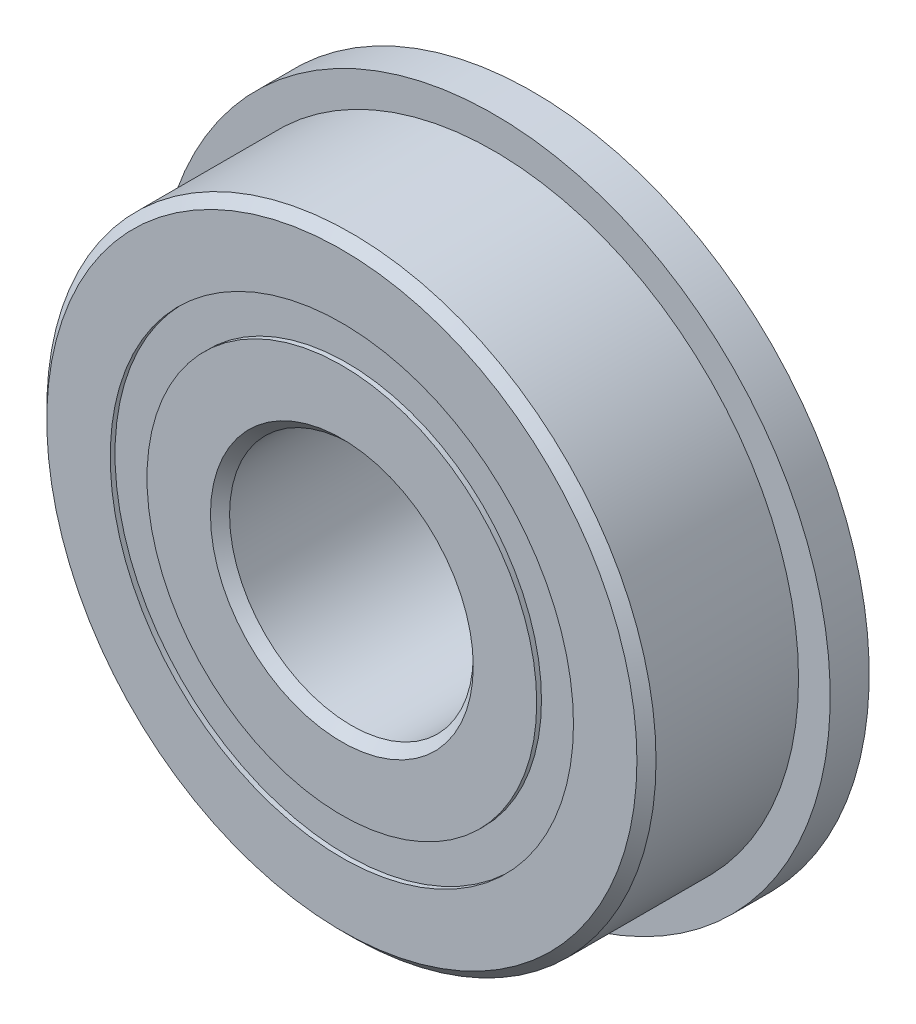
SolidWorks part; units mm, degrees
ref_plane "Front Plane" through (0, 0, 0) normal (0, 0, 1) x (1, 0, 0)
ref_plane "Top Plane" through (0, 0, 0) normal (0, 1, 0) x (1, 0, 0)
ref_plane "Right Plane" through (0, 0, 0) normal (1, 0, 0) x (0, 0, -1)
sketch "Sketch1" plane through (0, 0, 0) normal (1, 0, 0) x (0, 0, -1)
  line L0 (-2.4892, 0) -> (2.4892, 0) construction
  line L1 (0, 7.9375) -> (0, -7.9375) construction
  line L2 (2.2403, 7.9375) -> (-2.2403, 7.9375)
  line L3 (-2.2403, 7.9375) -> (-2.4892, 7.6886)
  line L4 (-2.4892, 7.6886) -> (-2.4892, 6.0352)
  line L5 (-2.4892, 6.0352) -> (-1.1063, 6.0352)
  line L6 (2.4892, 6.0352) -> (1.1063, 6.0352)
  line L7 (2.4892, 7.6886) -> (2.4892, 6.0352)
  line L8 (2.2403, 7.9375) -> (2.4892, 7.6886)
  line L9 (0, 7.9375) -> (0, 5.5563) construction
  line L10 (0, 5.5563) -> (0, 3.175) construction
  arc A0 (-1.1063, 6.0352) -> (1.1063, 6.0352) centre (0, 5.5563) cw
  point P14 (0, 3.175)
  dimension "D3" = 2.2126
  dimension "D1" = 45
  dimension "Width" = 4.9784
  dimension "OD" = 15.875
  dimension "D2" = 0.2489
  dimension "Shaft Dia" = 6.35
  dimension "D4" = 0.479
revolve "Revolve1" add sketch "Sketch1" angle 360 about L0
sketch "Sketch3" plane through (0, 0, 0) normal (1, 0, 0) x (0, 0, -1)
  line L0 (-2.4892, 5.0773) -> (-1.1063, 5.0773)
  line L1 (0, 7.9375) -> (0, -7.9375) construction
  line L2 (-2.4892, 7.6886) -> (-2.4892, 6.0352) construction
  line L3 (-2.4892, 5.0773) -> (-2.4892, 3.4239)
  line L4 (-2.2403, 7.9375) -> (-2.4892, 7.6886) construction
  line L5 (-2.4892, 3.4239) -> (-2.2403, 3.175)
  line L6 (-2.2403, 3.175) -> (2.2403, 3.175)
  line L7 (2.2403, 7.9375) -> (2.2403, -7.9375) construction
  line L8 (2.2403, 3.175) -> (2.4892, 3.4239)
  line L9 (2.4892, -7.6886) -> (2.4892, 7.6886) construction
  line L10 (2.4892, 3.4239) -> (2.4892, 5.0773)
  line L11 (2.4892, 5.0773) -> (1.1063, 5.0773)
  line L13 (2.2403, 7.9375) -> (2.4892, 7.6886) construction
  arc A0 (1.1063, 6.0352) -> (-1.1063, 6.0352) centre (0, 5.5563) ccw construction
  arc A1 (1.1063, 5.0773) -> (-1.1063, 5.0773) centre (0, 5.5562) cw
revolve "Revolve3" add sketch "Sketch3" angle 360 about L0
sketch "Sketch4" plane through (0, 0, 0) normal (1, 0, 0) x (0, 0, -1)
  line L0 (-1.2055, 5.5563) -> (1.2055, 5.5563)
  arc A2 (-1.2055, 5.5563) -> (1.2055, 5.5563) centre (0, 5.5563) cw
  arc A3 (1.1063, 6.0352) -> (-1.1063, 6.0352) centre (0, 5.5563) ccw construction
revolve "Revolve4" add sketch "Sketch4" angle 360 about L0
ref_axis "Axis1" through (0, 0, -2.4892) along (0, 0, 1)
pattern_circular "CirPattern1" count 14 every 25.714 about axis through (0, 0, -2.4892) along (0, 0, 1) of bodies 104
sketch "Sketch5" plane through (0, 0, 0) normal (1, 0, 0) x (0, 0, -1)
  line L0 (-2.4892, 6.0352) -> (-1.1063, 6.0352) construction
  line L1 (-2.3647, 6.0352) -> (-1.2055, 6.0352)
  line L2 (-2.3647, 6.0352) -> (-2.3647, 5.0773)
  line L3 (-2.3647, 5.0773) -> (-1.2055, 5.0773)
  line L4 (-1.2055, 6.0352) -> (-1.2055, 5.0773)
  line L5 (-2.4892, 5.0773) -> (-1.1063, 5.0773) construction
  line L6 (2.4892, 6.0352) -> (1.1063, 6.0352) construction
  line L7 (2.3647, 6.0352) -> (1.2055, 6.0352)
  line L8 (2.3647, 6.0352) -> (2.3647, 5.0773)
  line L9 (2.3647, 5.0773) -> (1.2055, 5.0773)
  line L10 (1.2055, 6.0352) -> (1.2055, 5.0773)
  line L11 (2.4892, 5.0773) -> (1.1063, 5.0773) construction
  line L12 (-2.2403, 7.9375) -> (-2.4892, 7.6886) construction
  point P18 (-2.3647, 7.813)
revolve "Revolve5" add sketch "Sketch5" angle 360 about L0
sketch "Sketch6" plane through (0, 0, 0) normal (1, 0, 0) x (0, 0, -1)
  line L0 (2.4892, 0) -> (-2.4892, 0) construction
  line L1 (2.4892, 6.0352) -> (1.4732, 6.0352)
  line L2 (2.4892, 6.0352) -> (2.4892, 8.763)
  line L3 (2.4892, 8.763) -> (1.4732, 8.763)
  line L4 (1.4732, 6.0352) -> (1.4732, 8.763)
  dimension "Th" = 1.016
  dimension "Flange OD" = 17.526
revolve "Revolve6" add sketch "Sketch6" angle 360 about L0
equation "\"D2@Sketch1\" = \"Width@Sketch1\"*.05"
equation "\"D3@Sketch1\" = \"Width@Sketch1\"/2.25"
equation "\"D4@Sketch1\" = (((\"OD@Sketch1\"-\"Width@Sketch1\")/2)/3.25)/3.5"
equation "\"D2@CirPattern1\" = 360/\"Balls@CirPattern1\""
